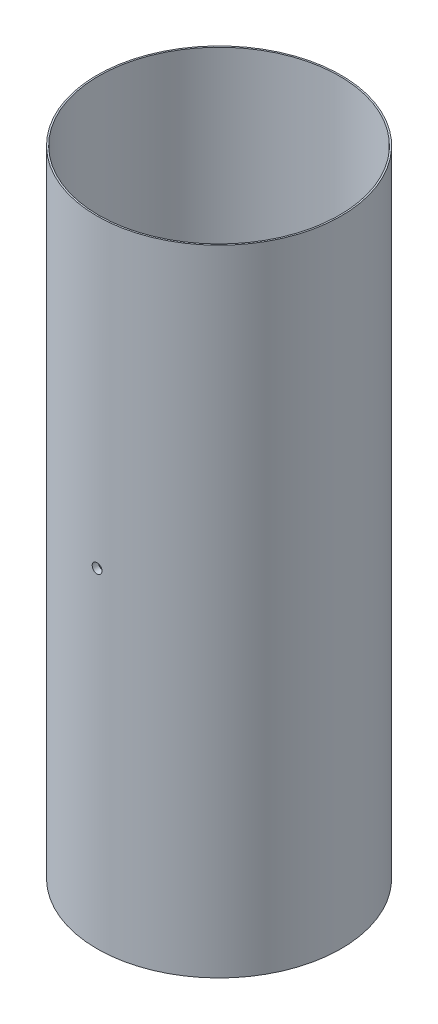
SolidWorks part; units mm, degrees
material "6061-T4 (SS)"
ref_plane "Front Plane" through (0, 0, 0) normal (0, 0, 1) x (1, 0, 0)
ref_plane "Top Plane" through (0, 0, 0) normal (0, 1, 0) x (1, 0, 0)
ref_plane "Right Plane" through (0, 0, 0) normal (1, 0, 0) x (0, 0, -1)
sketch "Sketch1" plane through (0, 0, 0) normal (0, 1, 0) x (1, 0, 0)
  circle A0 centre (0, 0) radius 63.5
  circle A1 centre (0, 0) radius 60.325
  dimension "D1" = 127
  dimension "D2" = 120.65
extrude "Boss-Extrude1" add sketch "Sketch1" along normal blind 330.2
sketch "Sketch5" plane through (0, 0, 0) normal (0, 1, 0) x (1, 0, 0)
  circle A0 centre (0, 0) radius 60.325
  circle A1 centre (0, 0) radius 62.7063
  dimension "D1" = 120.65
  dimension "D2" = 125.4125
extrude "Cut-Extrude1" cut sketch "Sketch5" along normal blind 158.75
sketch "Sketch6" plane through (0, 330.2, 0) normal (0, 1, 0) x (1, 0, 0)
  circle A0 centre (0, 0) radius 60.325
  circle A1 centre (0, 0) radius 62.7063
  dimension "D1" = 120.65
  dimension "D2" = 125.4125
extrude "Cut-Extrude2" cut sketch "Sketch6" against normal blind 120.65
ref_plane "Plane1" through (0, 0, 63.5) normal (0, 0, 1) x (1, 0, 0)
ref_plane "Plane2" through (0, 0, -63.5) normal (0, 0, 1) x (1, 0, 0)
sketch "Sketch8" plane through (0, 0, 63.5) normal (0, 0, 1) x (1, 0, 0)
  circle A0 centre (0, 171.45) radius 6.4556
  dimension "D1" = 171.45
sketch "Sketch12" plane through (0, 0, -63.5) normal (0, 0, 1) x (1, 0, 0)
  circle A0 centre (0, 171.45) radius 6.4556
hole_wizard "Tap Drill for 1/4-20 Tap8" positions "Sketch20" profile "Sketch19" hole size "1/4-20" standard "ANSI Inch" end condition up to next
sketch "Sketch20" plane through (0, 0, 63.5) normal (0, 0, 1) x (1, 0, 0)
  point P0 (0, 171.45)
sketch "Sketch19" plane through (0, 171.45, 63.5) normal (1, 0, 0) x (0, -1, 0)
  line L0 (0, 0) -> (0, 3.175)
  line L1 (0, 3.175) -> (2.5527, 3.175)
  line L2 (2.5527, 3.175) -> (2.5527, 0)
  line L5 (2.5527, 0) -> (0, 0)
  line L11 (0, -6.35) -> (0, 107.95) construction
  dimension "Thru Hole Dia." = 5.1054
  dimension "Thru Hole Depth" = 3.175
hole_wizard "Tap Drill for 1/4-20 Tap9" positions "Sketch21" profile "Sketch22" hole size "1/4-20" standard "ANSI Inch" end condition up to next
sketch "Sketch21" plane through (0, 0, -63.5) normal (0, 0, 1) x (1, 0, 0)
  point P0 (0, 171.45)
sketch "Sketch22" plane through (0, 171.45, -63.5) normal (1, 0, 0) x (0, 1, 0)
  line L0 (0, 0) -> (0, 3.175)
  line L1 (0, 3.175) -> (2.5527, 3.175)
  line L2 (2.5527, 3.175) -> (2.5527, 0)
  line L5 (2.5527, 0) -> (0, 0)
  line L11 (0, -6.35) -> (0, 107.95) construction
  dimension "Thru Hole Dia." = 5.1054
  dimension "Thru Hole Depth" = 3.175
ref_plane "Plane3" through (0, 313.5439, 0) normal (0, 1, 0) x (1, 0, 0)
sketch "Sketch24" plane through (0, 313.5439, 0) normal (0, 1, 0) x (1, 0, 0)
  circle A0 centre (0, 0) radius 60.325
